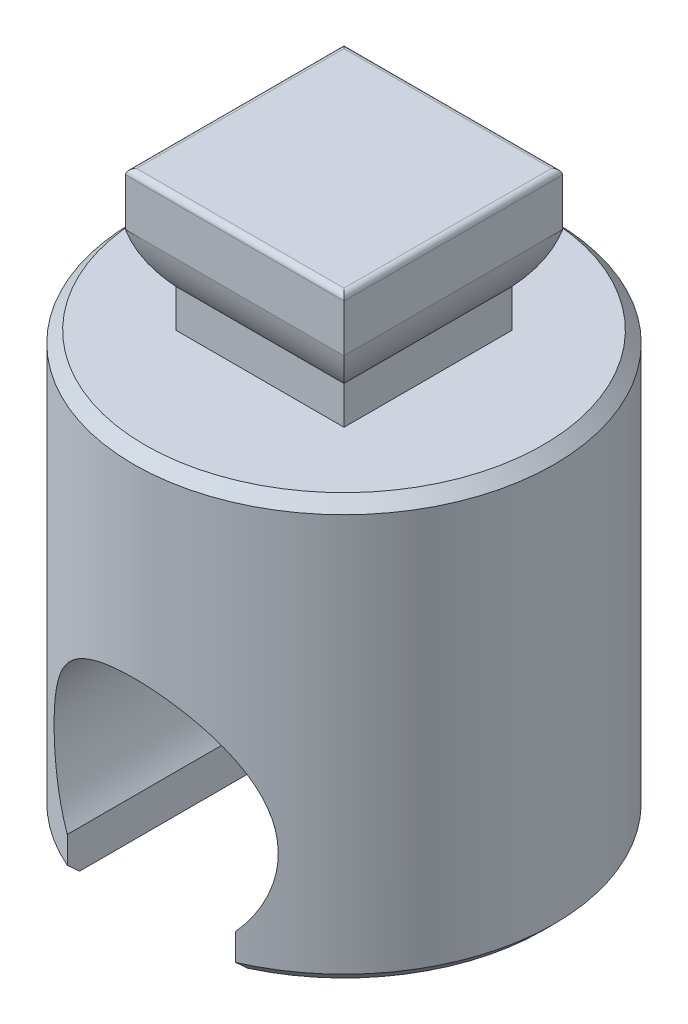
SolidWorks part; units mm, degrees
ref_plane "前视基准面" through (0, 0, 0) normal (0, 0, 1) x (1, 0, 0)
ref_plane "上视基准面" through (0, 0, 0) normal (0, 1, 0) x (1, 0, 0)
ref_plane "右视基准面" through (0, 0, 0) normal (1, 0, 0) x (0, 0, -1)
sketch "草图1" plane through (0, 0, 0) normal (0, 1, 0) x (1, 0, 0)
  circle A0 centre (0, 0) radius 3.75
  dimension "D1" = 7.5
extrude "凸台-拉伸1" add sketch "草图1" against normal blind 7.5
sketch "草图2" plane through (0, 0, 0) normal (0, 0, 1) x (1, 0, 0)
  line L0 (0, 0) -> (0, 2) construction
  line L1 (0, 2) -> (0, 2.5) construction
  line L2 (-1.95, 2.5) -> (1.95, 2.5)
  line L3 (1.95, 2.5) -> (1.95, 1.5556)
  line L4 (-1.5, 0) -> (1.5, 0)
  line L5 (3.75, 0) -> (-3.75, 0) construction
  line L6 (1.5, 0) -> (1.5, 0.6771)
  line L7 (-1.5, 0) -> (-1.5, 0.6771)
  line L8 (-1.95, 2.5) -> (-1.95, 1.5556)
  arc A0 (1.5, 0.6771) -> (1.95, 1.5556) centre (0, 2) ccw
  arc A1 (-1.5, 0.6771) -> (-1.95, 1.5556) centre (0, 2) cw
  dimension "D1" = 2
  dimension "D2" = 0.5
  dimension "D3" = 1.5
  dimension "D4" = 1.95
extrude "凸台-拉伸2" add sketch "草图2" along normal blind 2 and the other way blind 2
sketch "草图3" plane through (0, 0, 0) normal (1, 0, 0) x (0, 0, -1)
  line L0 (0, 0) -> (0, 2) construction
  line L1 (0, 2) -> (0, 2.5) construction
  line L2 (2, 2.5) -> (-2, 2.5) construction
  line L3 (0, 2.5) -> (1.95, 2.5) construction
  line L4 (1.95, 2.5) -> (1.95, 1.5556)
  line L5 (0, 0) -> (1.5, 0) construction
  line L6 (2, 0) -> (-2, 0) construction
  line L7 (1.5, 0) -> (1.5, 0.6771)
  line L8 (1.95, 2.5) -> (2, 2.5)
  line L9 (2, 2.5) -> (2, 0)
  line L10 (-2, 0) -> (-1.5, 0)
  line L11 (2, 0) -> (1.5, 0)
  line L12 (-2, 2.5) -> (-2, 0)
  line L13 (-1.95, 2.5) -> (-2, 2.5)
  line L14 (-1.5, 0) -> (-1.5, 0.6771)
  line L15 (-1.95, 2.5) -> (-1.95, 1.5556)
  arc A0 (1.5, 0.6771) -> (1.95, 1.5556) centre (0, 2) ccw
  arc A1 (-1.5, 0.6771) -> (-1.95, 1.5556) centre (0, 2) cw
  dimension "D1" = 2
  dimension "D2" = 1.5
  dimension "D3" = 1.95
extrude "切除-拉伸1" cut sketch "草图3" against normal blind 2 and the other way blind 2
sketch "草图4" plane through (0, 0, 0) normal (0, 0, 1) x (1, 0, 0)
  line L0 (0, -7.5) -> (0, -5.5) construction
  line L1 (-3.75, -7.5) -> (3.75, -7.5) construction
  line L2 (-1.5, -7.5) -> (1.5, -7.5)
  line L3 (1.5, -7.5) -> (1.5, -6.8229)
  line L4 (-1.5, -7.5) -> (-1.5, -6.8229)
  arc A0 (1.5, -6.8229) -> (-1.5, -6.8229) centre (0, -5.5) ccw
  dimension "D3" = 2
  dimension "D1" = 2
  dimension "D2" = 1.5
extrude "切除-拉伸2" cut sketch "草图4" against normal up to next and the other way up to next
fillet "圆角1" radius 0.1 4 edges at (0, 2.5, 1.95) (-1.95, 2.5, 0) (0, 2.5, -1.95) (1.95, 2.5, 0)
sketch "草图5" plane through (0, -7.5, 0) normal (0, -1, 0) x (1, 0, 0)
  circle A0 centre (0, 0) radius 0.75
  dimension "D1" = 1.5
extrude "切除-拉伸3" cut sketch "草图5" against normal blind 6
chamfer "倒角1" distance 0.2 angle 45 3 edges at (-3.75, -7.5, 0) (3.75, -7.5, 0) (0, 0, 3.75)
